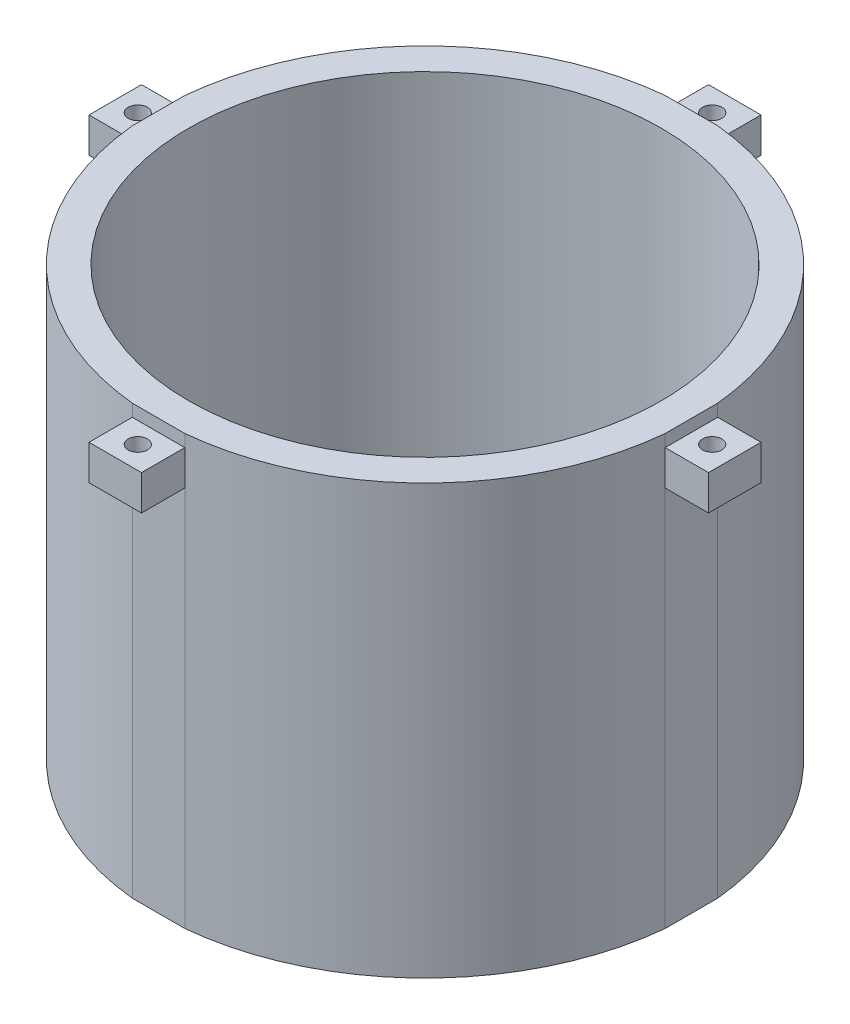
SolidWorks part; units mm, degrees
ref_plane "Ön Düzlem" through (0, 0, 0) normal (0, 0, 1) x (1, 0, 0)
ref_plane "Üst Düzlem" through (0, 0, 0) normal (0, 1, 0) x (1, 0, 0)
ref_plane "Sağ Düzlem" through (0, 0, 0) normal (1, 0, 0) x (0, 0, -1)
sketch "Sketch1" plane through (0, 0, 0) normal (0, 1, 0) x (1, 0, 0)
  circle A0 centre (0, 0) radius 135
  circle A1 centre (0, 0) radius 153
  dimension "D1" = 270
  dimension "D2" = 306
extrude "Boss-Extrude1" add sketch "Sketch1" along normal blind 245
sketch "Sketch3" plane through (0, 0, 0) normal (0, 1, 0) x (1, 0, 0)
  line L0 (152.2629, 15) -> (152.2629, -15)
  line L1 (15, 177) -> (-15, 177)
  line L2 (15, 177) -> (15, 152.2629)
  line L3 (-15, 177) -> (-15, 152.2629)
  line L4 (-15, 152.2629) -> (15, 152.2629)
  line L5 (177, -15) -> (152.2629, -15)
  line L6 (177, -15) -> (177, 15)
  line L7 (177, 15) -> (152.2629, 15)
  line L8 (15, -152.2629) -> (-15, -152.2629)
  line L9 (-15, -177) -> (-15, -152.2629)
  line L10 (-15, -177) -> (15, -177)
  line L11 (15, -177) -> (15, -152.2629)
  line L12 (-152.2629, -15) -> (-152.2629, 15)
  line L13 (-177, 15) -> (-152.2629, 15)
  line L14 (-177, 15) -> (-177, -15)
  line L15 (-177, -15) -> (-152.2629, -15)
  line L16 (0, 0) -> (15, 152.2629) construction
  line L17 (0, 0) -> (152.2629, -15) construction
  circle A4 centre (0, 0) radius 153 construction
  point P6 (0, 177)
  dimension "D1" = 4
  dimension "D2" = 90
  dimension "D3" = 30
  dimension "D4" = 24.7371
  dimension "D5" = 24.7371
  dimension "D6" = 30
extrude "Boss-Extrude3" add sketch "Sketch3" along normal through all contours L6 L7 L0 L5 | L10 L11 L8 L9 | L14 L15 L12 L13 | L4 L2 L1 L3 region at (164.6315, 0, 0) region at (0, 0, 164.6315) region at (-164.6315, 0, 0)
sketch "Sketch4" plane through (0, 0, 0) normal (0, -1, 0) x (1, 0, 0)
  line L0 (15, -177) -> (15, -152.2629)
  line L1 (15, -152.2629) -> (-15, -152.2629)
  line L2 (-15, -152.2629) -> (-15, -177)
  line L3 (-15, -177) -> (15, -177)
  line L4 (-177, 15) -> (-177, -15)
  line L5 (-177, -15) -> (-152.2629, -15)
  line L6 (-152.2629, -15) -> (-152.2629, 15)
  line L7 (-152.2629, 15) -> (-177, 15)
  line L8 (15, 177) -> (-15, 177)
  line L9 (-15, 177) -> (-15, 152.2629)
  line L10 (-15, 152.2629) -> (15, 152.2629)
  line L11 (15, 152.2629) -> (15, 177)
  line L12 (177, -15) -> (177, 15)
  line L13 (177, 15) -> (152.2629, 15)
  line L14 (152.2629, 15) -> (152.2629, -15)
  line L15 (152.2629, -15) -> (177, -15)
  point P25 (0, 0)
  dimension "D1" = 24.7371
  dimension "D2" = 30
  dimension "D3" = 24.7371
  dimension "D4" = 30
  dimension "D5" = 4
extrude "Cut-Extrude1" cut sketch "Sketch4" against normal blind 218 contours L3 L0 L1 L2 | L12 L13 L14 L15 | L8 L9 L10 L11 | L4 L5 L6 L7
sketch "Sketch5" plane through (0, 218, 0) normal (0, -1, 0) x (1, 0, 0)
  line L4 (0, -170) -> (0, -158.2629) construction
  circle A0 centre (0, -164.1315) radius 5.5
  circle A1 centre (-164.1315, 0) radius 5.5
  circle A2 centre (0, 164.1315) radius 5.5
  circle A3 centre (164.1315, 0) radius 5.5
  point P14 (0, 0)
  dimension "D1" = 4
  dimension "D2" = 164.1315
  dimension "D3" = 11.7371
extrude "Cut-Extrude2" cut sketch "Sketch5" against normal through all
sketch "Sketch6" plane through (0, 245, 0) normal (0, 1, 0) x (1, 0, 0)
  line L0 (177, 15) -> (152.2629, 15)
  line L1 (152.2629, 15) -> (152.2629, -15)
  line L2 (152.2629, -15) -> (177, -15)
  line L3 (177, -15) -> (177, 15)
  line L4 (-15, -177) -> (15, -177)
  line L5 (-15, -152.2629) -> (-15, -177)
  line L6 (15, -152.2629) -> (-15, -152.2629)
  line L7 (15, -177) -> (15, -152.2629)
  line L8 (-177, 15) -> (-177, -15)
  line L9 (-152.2629, 15) -> (-177, 15)
  line L10 (-152.2629, -15) -> (-152.2629, 15)
  line L11 (-177, -15) -> (-152.2629, -15)
  line L12 (15, 177) -> (-15, 177)
  line L13 (15, 152.2629) -> (15, 177)
  line L14 (-15, 152.2629) -> (15, 152.2629)
  line L15 (-15, 177) -> (-15, 152.2629)
  point P22 (0, 0)
  dimension "D1" = 24.7371
  dimension "D2" = 30
  dimension "D3" = 24.7371
  dimension "D4" = 30
  dimension "D5" = 4
extrude "Cut-Extrude3" cut sketch "Sketch6" against normal blind 7
sketch "Sketch7" plane through (0, 0, 0) normal (0, -1, 0) x (1, 0, 0)
  line L4 (-15, -152.2629) -> (15, -152.2629)
  line L5 (152.2629, -15) -> (152.2629, 15)
  line L6 (15, 152.2629) -> (-15, 152.2629)
  line L7 (-152.2629, 15) -> (-152.2629, -15)
  line L8 (-15, -152.2629) -> (15, -152.2629)
  line L9 (152.2629, -15) -> (152.2629, 15)
  line L10 (15, 152.2629) -> (-15, 152.2629)
  line L11 (-152.2629, 15) -> (-152.2629, -15)
  arc A4 (-152.2629, -15) -> (-15, -152.2629) centre (0, 0) ccw
  arc A5 (15, -152.2629) -> (152.2629, -15) centre (0, 0) ccw
  arc A6 (152.2629, 15) -> (15, 152.2629) centre (0, 0) ccw
  arc A7 (-15, 152.2629) -> (-152.2629, 15) centre (0, 0) ccw
  arc A8 (-152.2629, -15) -> (-15, -152.2629) centre (0, 0) ccw
  arc A9 (15, -152.2629) -> (152.2629, -15) centre (0, 0) ccw
  arc A10 (152.2629, 15) -> (15, 152.2629) centre (0, 0) ccw
  arc A11 (-15, 152.2629) -> (-152.2629, 15) centre (0, 0) ccw
  dimension "D1" = 0
